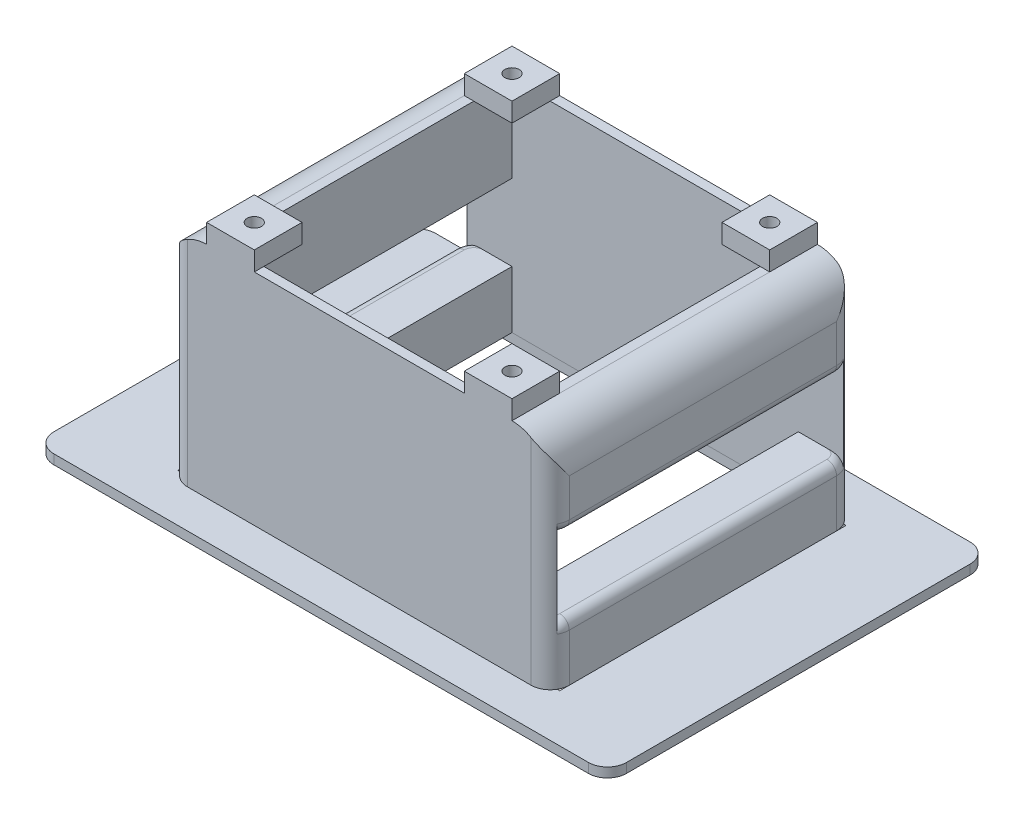
SolidWorks part; units mm, degrees
ref_plane "Front Plane" through (0, 0, 0) normal (0, 0, 1) x (1, 0, 0)
ref_plane "Top Plane" through (0, 0, 0) normal (0, 1, 0) x (1, 0, 0)
ref_plane "Right Plane" through (0, 0, 0) normal (1, 0, 0) x (0, 0, -1)
sketch "Sketch1" plane through (0, 0, 0) normal (0, 1, 0) x (1, 0, 0)
  line L1 (20, -15) -> (-20, -15)
  line L2 (20, -15) -> (20, 15)
  line L3 (20, 15) -> (-20, 15)
  line L4 (-20, -15) -> (-20, 15)
  line L5 (20, -15) -> (-20, 15) construction
  line L6 (20, 15) -> (-20, -15) construction
  line L7 (30, -20) -> (-30, -20)
  line L8 (30, -20) -> (30, 20)
  line L9 (30, 20) -> (-30, 20)
  line L10 (-30, -20) -> (-30, 20)
  line L11 (30, -20) -> (-30, 20) construction
  line L12 (30, 20) -> (-30, -20) construction
  point P0 (0, 0)
  point P6 (0, 0)
  dimension "D1" = 30
  dimension "D2" = 40
  dimension "D3" = 5
  dimension "D4" = 10
extrude "Boss-Extrude1" add sketch "Sketch1" along normal blind 1
sketch "Sketch2" plane through (0, 1, 0) normal (0, 1, 0) x (1, 0, 0)
  line L2 (20, -15) -> (20, 15)
  line L4 (-20, -15) -> (-20, 15)
  line L8 (15, -15) -> (15, 15)
  line L10 (-15, -15) -> (-15, 15)
  line L11 (-15, 15) -> (15, 15)
  line L12 (-20, 15) -> (-20, 16)
  line L13 (-20, 16) -> (20, 16)
  line L14 (20, 15) -> (20, 16)
  line L15 (15, -15) -> (-15, -15)
  line L16 (20, -15) -> (20, -16)
  line L17 (20, -16) -> (-20, -16)
  line L18 (-20, -15) -> (-20, -16)
  point P0 (0, 0)
  point P7 (0, 0)
  dimension "D1" = 30
  dimension "D2" = 30
  dimension "D3" = 1
  dimension "D4" = 1
extrude "Boss-Extrude2" add sketch "Sketch2" along normal blind 14 separate body
sketch "Sketch3" plane through (20, 0, 0) normal (1, 0, 0) x (0, 0, -1)
  line L0 (-16, 15) -> (16, 15) construction
  line L1 (-15, 15) -> (15, 15)
  line L2 (-15, 15) -> (-15, 7)
  line L3 (-15, 7) -> (15, 7)
  line L4 (15, 15) -> (15, 7)
  line L5 (-16, 15) -> (-16, 1) construction
  line L6 (16, 15) -> (16, 1) construction
  dimension "D1" = 1
  dimension "D2" = 1
  dimension "D3" = 8
extrude "Cut-Extrude1" cut sketch "Sketch3" against normal through all
sketch "Sketch4" plane through (0, 15, 0) normal (0, 1, 0) x (1, 0, 0)
  line L0 (-20, -15) -> (20, -15) construction
  line L1 (-20, 16) -> (20, 16)
  line L2 (-20, 16) -> (-20, -16)
  line L3 (-20, -16) -> (20, -16)
  line L4 (20, 16) -> (20, -16)
  line L5 (-20, 16) -> (20, -16) construction
  line L6 (-20, -16) -> (20, 16) construction
  line L7 (-15, 15) -> (15, 15)
  line L8 (-15, 15) -> (-15, -15)
  line L9 (-15, -15) -> (15, -15)
  line L10 (15, 15) -> (15, -15)
  line L11 (-15, 15) -> (15, -15) construction
  line L12 (-15, -15) -> (15, 15) construction
  line L13 (15, -15) -> (20, -15) construction
  point P0 (0, 0)
  point P7 (0, 0)
extrude "Boss-Extrude3" add sketch "Sketch4" along normal blind 9
fillet "Fillet1" radius 2 4 edges at (30, 0.5, -20) (-30, 0.5, -20) (-30, 0.5, 20) (30, 0.5, 20)
fillet "Fillet2" radius 2 4 edges at (20, 12.5, -16) (20, 12.5, 16) (-20, 12.5, -16) (-20, 12.5, 16)
fillet "Fillet4" radius 1 12 edges at (-19.9319, 7, 14.5176) (-19.9319, 7, -14.5176) (-19.9319, 15, -14.5176) (-19.9319, 15, 14.5176) (19.9319, 7, 14.5176) (19.9319, 7, -14.5176) (19.9319, 15, 14.5176) (19.9319, 15, -14.5176) (-20, 7, 0) (-20, 15, 0) (20, 7, 0) (20, 15, 0)
sketch "Sketch5" plane through (0, 0, 16) normal (0, 0, 1) x (1, 0, 0)
  line L0 (-20, 20) -> (-20, 24)
  line L1 (-20, 24) -> (-16, 24)
  line L2 (20, 20) -> (20, 24)
  line L3 (20, 24) -> (16, 24)
  arc A0 (16, 24) -> (20, 20) centre (16, 20) cw
  arc A1 (-16, 24) -> (-20, 20) centre (-16, 20) ccw
  point P9 (20, 24)
  point P12 (-20, 24)
  dimension "D1" = 4
extrude "Cut-Extrude2" cut sketch "Sketch5" against normal through all
sketch "Sketch7" plane through (0, 24, 0) normal (0, 1, 0) x (1, 0, 0)
  line L0 (-16, -16) -> (16, -16) construction
  line L1 (-13.5, -13.5) -> (13.5, -13.5) construction
  line L2 (-13.5, -13.5) -> (-13.5, 13.5) construction
  line L3 (-13.5, 13.5) -> (13.5, 13.5) construction
  line L4 (13.5, -13.5) -> (13.5, 13.5) construction
  line L5 (-13.5, -13.5) -> (13.5, 13.5) construction
  line L6 (-13.5, 13.5) -> (13.5, -13.5) construction
  line L7 (-11, 11) -> (-16, 11)
  line L8 (-11, 11) -> (-11, 16)
  line L9 (-11, 16) -> (-16, 16)
  line L10 (-16, 11) -> (-16, 16)
  line L11 (-11, 11) -> (-16, 16) construction
  line L12 (-11, 16) -> (-16, 11) construction
  line L13 (11, 11) -> (16, 11)
  line L14 (11, 11) -> (11, 16)
  line L15 (11, 16) -> (16, 16)
  line L16 (16, 11) -> (16, 16)
  line L17 (11, 11) -> (16, 16) construction
  line L18 (11, 16) -> (16, 11) construction
  line L19 (11, -11) -> (16, -11)
  line L20 (11, -11) -> (11, -16)
  line L21 (11, -16) -> (16, -16)
  line L22 (16, -11) -> (16, -16)
  line L23 (11, -11) -> (16, -16) construction
  line L24 (11, -16) -> (16, -11) construction
  line L25 (16, 16) -> (16, -16) construction
  line L27 (-11, -11) -> (-16, -11)
  line L28 (-11, -11) -> (-11, -16)
  line L29 (-11, -16) -> (-16, -16)
  line L30 (-16, -11) -> (-16, -16)
  line L31 (-11, -11) -> (-16, -16) construction
  line L32 (-11, -16) -> (-16, -11) construction
  circle A0 centre (-13.5, 13.5) radius 0.75
  circle A1 centre (13.5, 13.5) radius 0.75
  circle A2 centre (13.5, -13.5) radius 0.75
  circle A3 centre (-13.5, -13.5) radius 0.75
  point P0 (0, 0)
  point P16 (0, 0)
  dimension "D3" = 1.5
  dimension "D1" = 27
  dimension "D2" = 27
  dimension "D4" = 4
extrude "Boss-Extrude5" add sketch "Sketch7" along normal blind 2
